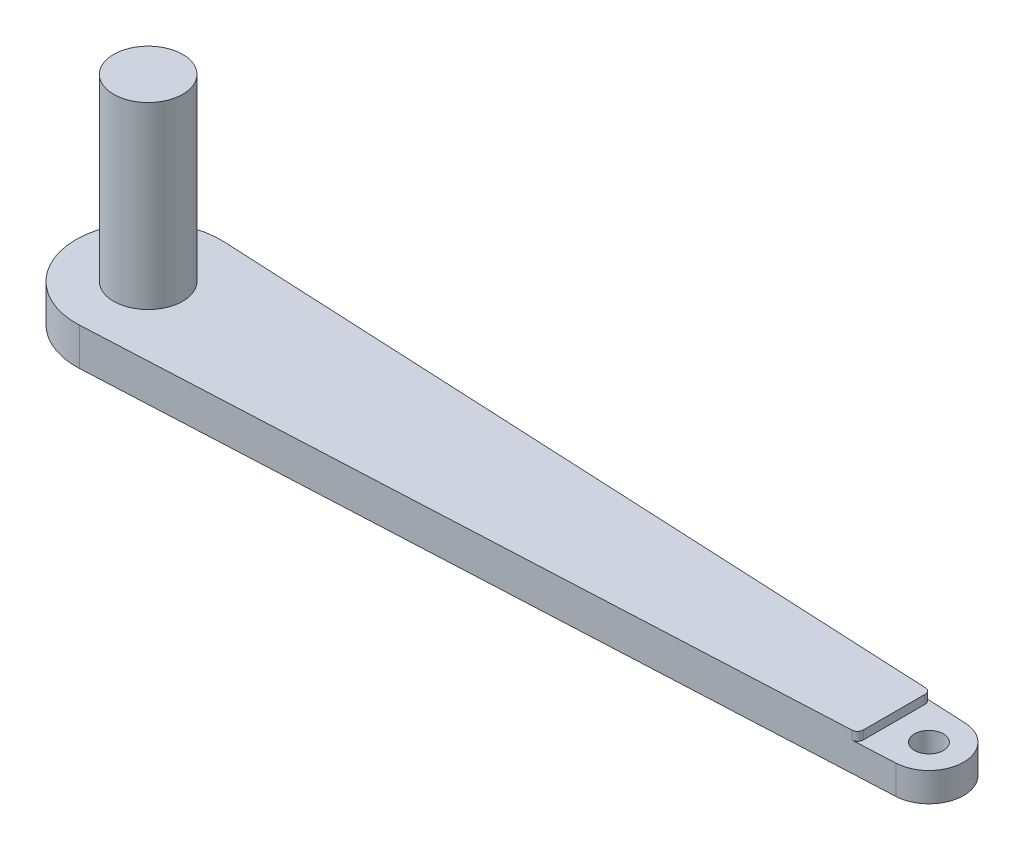
SolidWorks part; units mm, degrees
ref_plane "Front Plane" through (0, 0, 0) normal (0, 0, 1) x (1, 0, 0)
ref_plane "Top Plane" through (0, 0, 0) normal (0, 1, 0) x (1, 0, 0)
ref_plane "Right Plane" through (0, 0, 0) normal (1, 0, 0) x (0, 0, -1)
sketch "Sketch2" plane through (0, 0, 0) normal (0, 1, 0) x (1, 0, 0)
  line L0 (-36.4106, 0) -> (117.0894, 0) construction
  line L1 (-23.3087, 12.4855) -> (111.3783, 5.993)
  line L2 (-23.3087, -12.4855) -> (111.3783, -5.993)
  circle A0 centre (111.0894, 0) radius 2.5
  arc A1 (111.3783, -5.993) -> (111.3783, 5.993) centre (111.0894, 0) ccw
  arc A2 (-23.3087, 12.4855) -> (-23.3087, -12.4855) centre (-23.9106, 0) ccw
  circle A3 centre (-23.9106, 0) radius 6
  dimension "D1" = 12
  dimension "D2" = 5
  dimension "D3" = 25
  dimension "D5" = 12
  dimension "D4" = 135
extrude "Boss-Extrude1" add sketch "Sketch2" along normal blind 6.5
sketch "Sketch3" plane through (0, 6.5, 0) normal (0, 1, 0) x (1, 0, 0)
  circle A0 centre (-23.9106, 0) radius 6
extrude "Boss-Extrude2" add sketch "Sketch3" against normal up to surface (6.5 mm away) up to face at (42.1871, 0, 0)
sketch "Sketch4" plane through (0, 6.5, 0) normal (0, 1, 0) x (1, 0, 0)
  circle A0 centre (-23.9106, 0) radius 5.975
  dimension "D1" = 11.95
extrude "Boss-Extrude3" add sketch "Sketch4" along normal blind 31 contours A0
sketch "Sketch5" plane through (0, 0, 0) normal (0, -1, 0) x (1, 0, 0)
  circle A0 centre (-23.9106, 0) radius 2.825
  dimension "D1" = 5.65
extrude "Cut-Extrude1" cut sketch "Sketch5" against normal blind 9
chamfer "Chamfer1" distance 0.5 angle 45 1 edges at (-23.9106, 0, -2.825)
sketch "Sketch6" plane through (0, 6.5, 0) normal (0, 1, 0) x (1, 0, 0)
  line L0 (105.0894, 0) -> (105.0894, 15.9577)
  line L1 (105.0894, 15.9577) -> (127.6962, 15.9577)
  line L2 (127.6962, 15.9577) -> (127.6962, -15.6622)
  line L3 (127.6962, -15.6622) -> (105.0894, -15.6622)
  line L4 (105.0894, -15.6622) -> (105.0894, 0)
  circle A0 centre (111.0894, 0) radius 2.5 construction
  dimension "D1" = 6
extrude "Cut-Extrude2" cut sketch "Sketch6" against normal blind 1.5
fillet "Fillet1" radius 1 2 edges at (105.0894, 5.75, -6.2962) (105.0894, 5.75, 6.2962)
